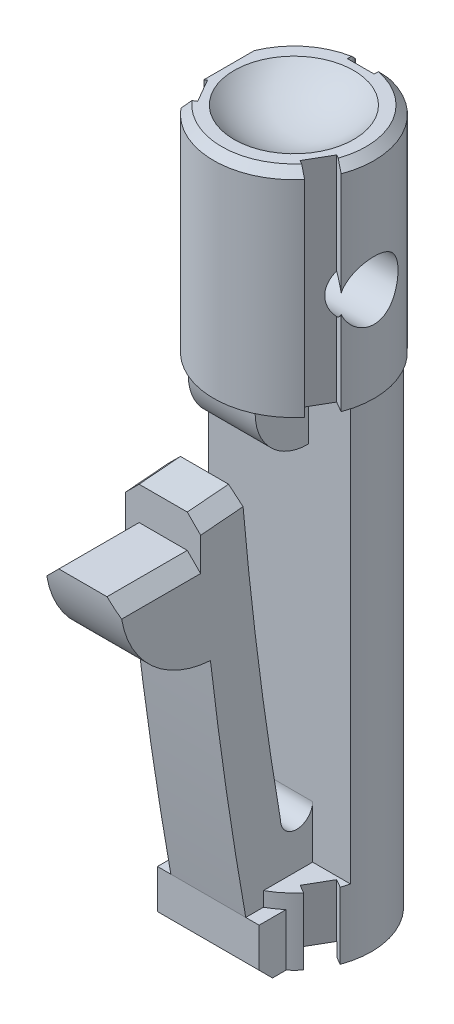
SolidWorks part; units mm, degrees
ref_plane "정면" through (0, 0, 0) normal (0, 0, 1) x (1, 0, 0)
ref_plane "윗면" through (0, 0, 0) normal (0, 1, 0) x (1, 0, 0)
ref_plane "우측면" through (0, 0, 0) normal (1, 0, 0) x (0, 0, -1)
sketch "스케치2" plane through (0, 0, 0) normal (1, 0, 0) x (0, 0, -1)
  line L0 (-2.5, 2.5) -> (-2.5, 0)
  line L1 (0, 0) -> (0, 16)
  line L2 (0, 16) -> (-2.5, 16)
  line L3 (-2.5, 16) -> (-2.5, 2.5)
  line L4 (0, 16) -> (-6.5, 16) construction
  line L5 (-5.5657, 21.6648) -> (-6.5657, 21.6648) construction
  line L6 (-5, 0) -> (-2.5, 0)
  line L7 (-7.1481, 18.9755) -> (-9.1481, 18.9755) construction
  line L8 (-9.1481, 18.9755) -> (-9.1481, 18.4755)
  line L9 (-9.1481, 18.4755) -> (-7.036, 16.9755) construction
  line L10 (-7.1481, 18.9755) -> (-6.6861, 18.9755) construction
  line L11 (-5, 0) -> (-5, -1.9599)
  line L12 (-5, -1.9599) -> (0, -1.9599)
  line L13 (0, -1.9599) -> (0, 0)
  line L14 (-2.5, 0) -> (0, 0) construction
  line L15 (-6.6861, 18.9755) -> (-6.5657, 21.6648) construction
  line L16 (-6.6861, 12.4755) -> (-9.6861, 12.4755)
  line L17 (-4.5, 16) -> (-2.5, 16)
  line L18 (-5.1425, 13.8456) -> (-6.6861, 13.7165)
  line L19 (-6.6861, 13.7165) -> (-6.6861, 12.4755)
  arc A0 (-2.5, 2.5) -> (-3.7, 2.5) centre (-3.1, 2.5) cw
  arc A1 (-5, 0) -> (-7.1481, 18.9755) centre (143.4031, 26.4092) cw construction
  arc A2 (-3.7, 2.5) -> (-5.5657, 21.6648) centre (127.5008, 24.9454) cw construction
  arc A3 (-9.6861, 12.4755) -> (-6.32, 8.9755) centre (-6.0873, 12.5681) ccw
  arc A4 (-2.5, 14) -> (-4.5, 16) centre (-2.5, 16) cw
  arc A5 (-9.1481, 18.4755) -> (-6.9854, 16.2004) centre (-5.687, 19.6001) ccw construction
  arc A6 (-5, 0) -> (-6.6861, 12.4755) centre (143.4031, 26.4092) cw
  arc A7 (-3.7, 2.5) -> (-5.1425, 13.8456) centre (127.5008, 24.9454) cw
  dimension "D1" = 16
  dimension "D2" = 5
  dimension "D3" = 2.5
  dimension "D4" = 6.5
  dimension "D5" = 0.5
  dimension "D6" = 2
  dimension "D7" = 3.1
  dimension "D8" = 2
  dimension "D9" = 1
  dimension "D10" = 2.5
  dimension "D11" = 4.5
  dimension "D12" = 3
  dimension "D13" = 3.5
  dimension "D14" = 2
extrude "보스-돌출1" add sketch "스케치2" along normal mid plane 3.8 contours L12 L13 L1 L2 L3 L0 L6 L11 region at (0, 6.2329, 1.496)
extrude "보스-돌출2" add sketch "스케치2<3>" along normal mid plane 2.8 contours A0 A2 L5 L15 L10 A1 L6 L0 | L9 A1 L7 L8 | L16 A3 A1 region at (0, 6.3813, 4.9843) region at (0, 10.9924, 7.835)
sketch "스케치2<3>" plane through (0, 0, 0) normal (1, 0, 0) x (0, 0, -1) same geometry as "스케치2"
sketch "스케치3" plane through (0, 16, 0) normal (0, 1, 0) x (1, 0, 0)
  line L0 (0, -1.8) -> (0, 0) construction
  circle A0 centre (0, -1.8) radius 3
  dimension "D1" = 6
  dimension "D2" = 1.8
extrude "보스-돌출3" add sketch "스케치3" along normal blind 8
extrude "보스-돌출4" add sketch "스케치2<4>" along normal mid plane 2.5 contours A4 L3 L17 region at (0, 15.1512, 3.3488)
sketch "스케치2<4>" plane through (0, 0, 0) normal (1, 0, 0) x (0, 0, -1) same geometry as "스케치2"
sketch "스케치4" plane through (0, -1.9599, 0) normal (0, -1, 0) x (1, 0, 0)
  circle A0 centre (0, 1.8) radius 2.9
  dimension "D1" = 5.8
extrude "보스-돌출5" add sketch "스케치4" against normal blind 2.5
sketch "스케치6" plane through (0, -1.9599, 0) normal (0, -1, 0) x (1, 0, 0)
  circle A0 centre (0, 1.8) radius 2.6
  dimension "D1" = 5.2
extrude "컷-돌출1" cut sketch "스케치6" against normal blind 0.5
sketch "스케치7" plane through (0, 0.5401, 0) normal (0, 1, 0) x (1, 0, 0)
  line L0 (-2.8142, -2.5) -> (2.8142, -2.5)
  arc A0 (2.8142, -2.5) -> (-2.8142, -2.5) centre (0, -1.8) ccw
  dimension "D1" = 5.8
  dimension "D2" = 2.5
extrude "보스-돌출6" add sketch "스케치7" along normal blind 20
sketch "스케치8" plane through (0, 0, 0) normal (1, 0, 0) x (0, 0, -1)
  line L0 (-1.8, 0) -> (0, 0) construction
  line L1 (-1.8, 0) -> (-1.8, 19.5) construction
  circle A0 centre (-1.8, 19.5) radius 1.1
  dimension "D2" = 2.2
  dimension "D1" = 1.8
  dimension "D3" = 19.5
extrude "컷-돌출2" cut sketch "스케치8" against normal through all both and the other way through all
chamfer "모따기1" distance 0.3 angle 45 1 edges at (0, 24, 4.8)
chamfer "모따기2" distance 0.5 angle 45 1 edges at (0, -1.9599, 5)
chamfer "모따기3" distance 0.5 angle 45 4 edges at (1.4, 12.4755, 8.1861) (-1.4, 12.4755, 8.1861) (1.4, 13.7811, 5.9143) (-1.4, 13.7811, 5.9143)
sketch "스케치9" plane through (0, 24, 0) normal (0, 1, 0) x (1, 0, 0)
  line L0 (0, 1.2) -> (0, 0) construction
  line L1 (-0.5, 1.7) -> (0.5, 1.7)
  line L2 (-0.5, 1.7) -> (-0.5, 0.7)
  line L3 (-0.5, 0.7) -> (0.5, 0.7)
  line L4 (0.5, 1.7) -> (0.5, 0.7)
  line L5 (-0.5, 1.7) -> (0.5, 0.7) construction
  line L6 (-0.5, 0.7) -> (0.5, 1.7) construction
  circle A0 centre (0, -1.8) radius 3 construction
  point P0 (0, 1.2)
  dimension "D3" = 1
  dimension "D4" = 1
extrude "컷-돌출3" cut sketch "스케치9" against normal through all
sketch "스케치10" plane through (0, 0, 0) normal (0, 1, 0) x (1, 0, 0)
  line L0 (0, 0) -> (0, -11.399) construction
  line L1 (-6.2975, 2.281) -> (-2.5, 2.281)
  line L2 (-6.2975, 2.281) -> (-6.2975, -6.3662)
  line L3 (-6.2975, -6.3662) -> (-2.5, -6.3662)
  line L4 (-2.5, 2.281) -> (-2.5, -6.3662)
  dimension "D1" = 2.5
fillet "필렛1" radius 0.2 2 edges at (0.5, 19.85, -1.158) (-0.5, 19.85, -1.158)
extrude "컷-돌출4" cut sketch "스케치10" against normal through all both and the other way through all
pattern_circular "원형 패턴1" count 3 over 360 about axis through (0, 24, 1.8) along (0, -1, 0) of "컷-돌출3"
sketch "스케치11" plane through (0, -1.4599, 0) normal (0, -1, 0) x (1, 0, 0)
  circle A0 centre (-2.1318, 2.2776) radius 0.9982
extrude "컷-돌출5" cut sketch "스케치11" along normal blind 10
sketch "스케치12" plane through (0, 0, 0) normal (1, 0, 0) x (0, 0, -1)
  line L0 (-1.8, 19.5) -> (-1.8, 39.1148) construction
  line L1 (-1.8, 29) -> (-1.8, 23)
  arc A0 (-1.8, 23) -> (-1.8, 29) centre (-1.8, 26) ccw
  dimension "D1" = 3
  dimension "D2" = 3.5
revolve "컷-회전1" cut sketch "스케치12" angle 360 about L0
